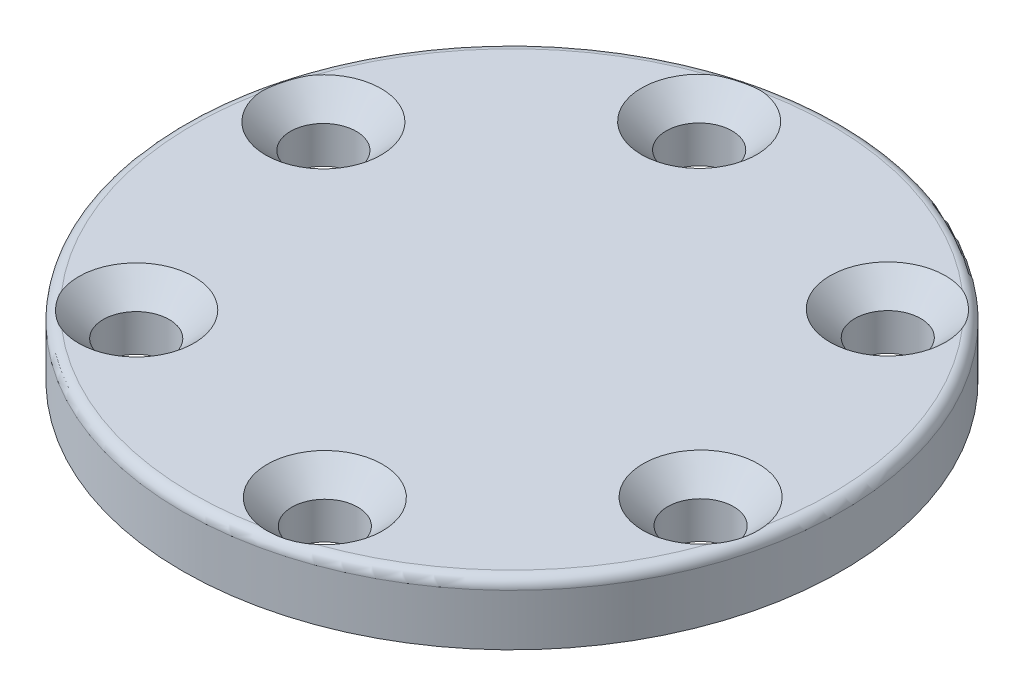
SolidWorks part; units mm, degrees
ref_plane "Front Plane" through (0, 0, 0) normal (0, 0, 1) x (1, 0, 0)
ref_plane "Top Plane" through (0, 0, 0) normal (0, 1, 0) x (1, 0, 0)
ref_plane "Right Plane" through (0, 0, 0) normal (1, 0, 0) x (0, 0, -1)
sketch "Sketch1" plane through (0, 0, 0) normal (0, 1, 0) x (1, 0, 0)
  circle A0 centre (23.7718, 10.3791) radius 1.6
  circle A2 centre (36.2396, 7.0682) radius 1.6
  circle A3 centre (39.6063, -5.3847) radius 1.6
  circle A4 centre (30.505, -14.5268) radius 1.6
  circle A5 centre (18.0371, -11.2159) radius 1.6
  circle A6 centre (14.6705, 1.237) radius 1.6
  circle A7 centre (27.1384, -2.0738) radius 16
  point P14 (27.1384, -2.0738)
  point P15 (0, 0)
  dimension "D2" = 3.2
  dimension "D3" = 3.2
  dimension "D4" = 3.2
  dimension "D5" = 3.2
  dimension "D6" = 3.2
  dimension "D7" = 3.2
extrude "Boss-Extrude1" add sketch "Sketch1" along normal blind 3
chamfer "Chamfer1" distance 1.2 angle 45 6 edges at (18.0371, 3, 12.8159) (30.505, 3, 16.1268) (39.6063, 3, 6.9847) (36.2396, 3, -5.4682) (23.7718, 3, -8.7791) (14.6705, 3, 0.363)
fillet "Fillet1" radius 0.5 1 edges at (27.1384, 3, 18.0738)
